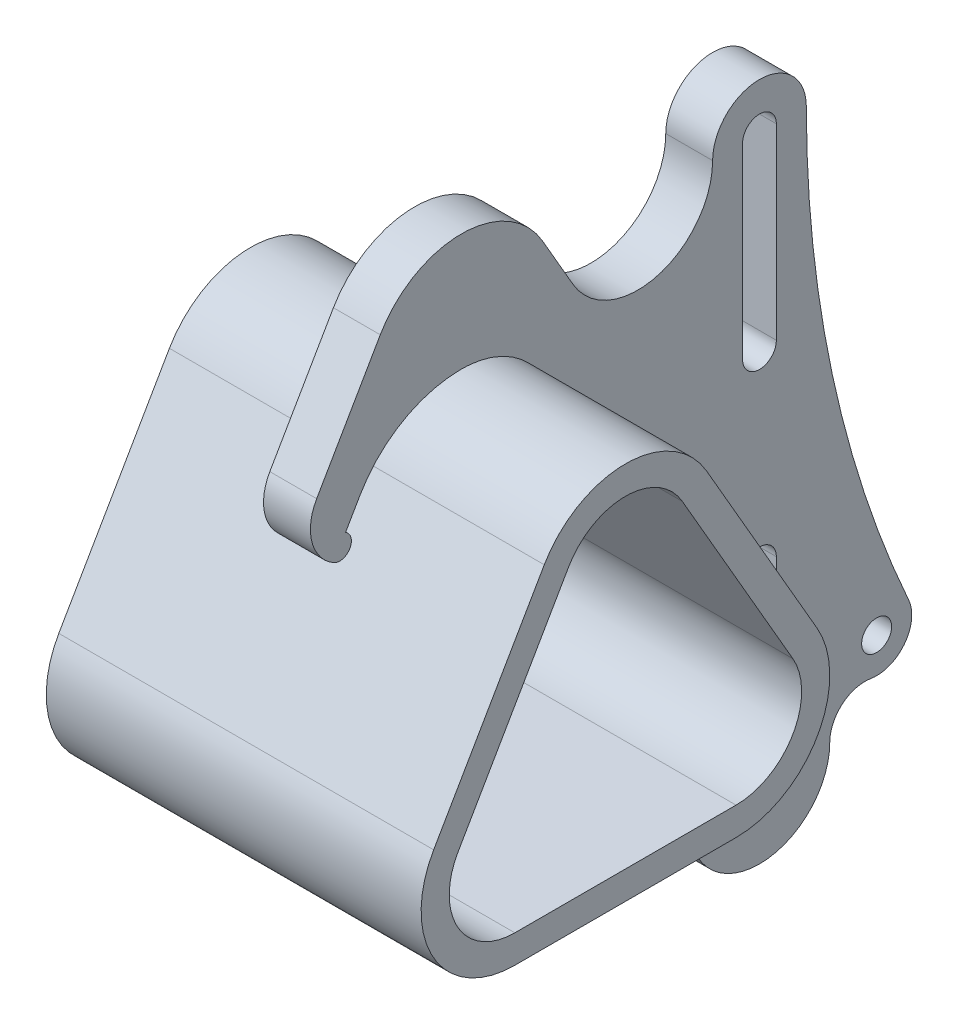
SolidWorks part; units mm, degrees
ref_plane "Front Plane" through (0, 0, 0) normal (0, 0, 1) x (1, 0, 0)
ref_plane "Top Plane" through (0, 0, 0) normal (0, 1, 0) x (1, 0, 0)
ref_plane "Right Plane" through (0, 0, 0) normal (1, 0, 0) x (0, 0, -1)
sketch "Sketch1" plane through (0, 0, 0) normal (1, 0, 0) x (0, 0, -1)
  line L0 (-9.525, 0) -> (-9.525, 27.9956)
  line L1 (-9.525, 27.9956) -> (-29.3888, 62.4007)
  line L2 (-14.4015, 36.4419) -> (-29.3888, 62.4007)
  line L3 (-51.3858, 62.4007) -> (-66.3732, 36.4419)
  line L4 (-55.3746, 17.3919) -> (-25.4, 17.3919)
  line L5 (-55.3746, 21.2019) -> (-25.4, 21.2019)
  line L6 (-48.0863, 60.4957) -> (-63.0736, 34.5369)
  line L7 (-17.701, 34.5369) -> (-32.6884, 60.4957)
  line L8 (-12.7, 30.0919) -> (-12.7, 3.0715) construction
  line L9 (-51.3858, 62.4007) -> (-47.8363, 68.5487) construction
  line L10 (-54.1355, 60.8132) -> (-56.0914, 57.4255)
  line L11 (-60.0031, 63.3501) -> (-51.3858, 78.2757)
  line L12 (-29.3888, 78.2757) -> (-25.2644, 71.1319)
  line L13 (-40.3873, 71.9257) -> (-23.8895, 71.9257) construction
  line L14 (-56.8851, 56.0507) -> (-40.3873, 56.0507) construction
  arc A0 (-9.525, 0) -> (9.525, 0) centre (0, 0) ccw
  arc A1 (-29.3888, 62.4007) -> (-40.3873, 68.7507) centre (-40.3873, 56.0507) ccw
  arc A2 (-14.4015, 36.4419) -> (-25.4, 17.3919) centre (-25.4, 30.0919) cw
  arc A3 (-29.3888, 62.4007) -> (-51.3858, 62.4007) centre (-40.3873, 56.0507) ccw
  arc A4 (-66.3732, 36.4419) -> (-55.3746, 17.3919) centre (-55.3746, 30.0919) ccw
  arc A5 (-17.701, 34.5369) -> (-25.4, 21.2019) centre (-25.4, 30.0919) cw
  arc A6 (-63.0736, 34.5369) -> (-55.3746, 21.2019) centre (-55.3746, 30.0919) ccw
  arc A7 (-32.6884, 60.4957) -> (-48.0863, 60.4957) centre (-40.3873, 56.0507) ccw
  arc A8 (-40.3873, 68.7507) -> (-51.3858, 62.4007) centre (-40.3873, 56.0507) ccw construction
  arc A9 (-40.3873, 68.7507) -> (-54.1355, 60.8132) centre (-40.3873, 52.8757) ccw
  arc A10 (-56.0914, 57.4255) -> (-57.6789, 54.6758) centre (-56.8851, 56.0507) cw
  arc A11 (-57.6789, 54.6758) -> (-60.0031, 63.3501) centre (-54.5039, 60.1751) cw
  arc A12 (-51.3858, 78.2757) -> (-29.3888, 78.2757) centre (-40.3873, 71.9257) cw
  arc A13 (-29.3888, 62.4007) -> (-51.3858, 62.4007) centre (-40.3873, 56.0507) ccw construction
  arc A14 (-25.2644, 71.1319) -> (-23.893, 73.5132) centre (-23.8895, 71.9257) ccw construction
  arc A16 (-6.35, 76.2) -> (6.35, 76.2) centre (0, 76.2) cw
  arc A17 (9.525, 0) -> (15.0813, 4.6959) centre (14.2875, 0) cw
  arc A18 (15.0813, 4.6959) -> (20.2209, 11.3397) centre (15.875, 9.3918) ccw
  arc A20 (6.35, 76.2) -> (20.2209, 11.3397) centre (164.9286, 76.2) ccw
  arc A21 (-66.3732, 36.4419) -> (-55.3746, 17.3919) centre (-55.3746, 30.0919) ccw construction
  arc A22 (-32.6884, 60.4957) -> (-48.0863, 60.4957) centre (-40.3873, 56.0507) ccw construction
  arc A23 (-25.2644, 71.1319) -> (-6.35, 76.2) centre (-16.4862, 76.2) ccw
  point P11 (-40.3873, 79.496)
  point P17 (-40.3873, 68.7507)
  point P18 (-40.3873, 17.3919)
  point P27 (-55.3746, 18.8051)
  point P45 (-40.3873, 97.3257)
  point P55 (0, 0)
  dimension "D1" = 12.7
  dimension "D6" = 60
  dimension "D7" = 1.5875
  dimension "D8" = 1.5875
  dimension "D9" = 12.7
  dimension "D12" = 6.35
  dimension "D13" = 9.525
  dimension "D15" = 4.7625
  dimension "D2" = 51.3588
  dimension "D4" = 3.175
  dimension "D5" = 150
  dimension "D10" = 6.35
  dimension "D11" = 12.7
  dimension "D14" = 15.875
  dimension "D16" = 76.2
  dimension "D3" = 3.81
extrude "Boss-Extrude1" add sketch "Sketch1" along normal mid plane 6.35 contours A23 L12 A12 L11 A11 A10 L10 A9 A1 L1 L0 A0 A17 A18 A20 A16 region at (0, 42.9084, 9.4146)
extrude "Boss-Extrude2" add sketch "Sketch1<3>" along normal mid plane 50.8 separate body contours L3 A4 L4 A2 L1 A1 A3 A7 L7 A5 L5 A6 L6 region at (0, 24.1195, 15.0555)
sketch "Sketch1<3>" plane through (0, 0, 0) normal (1, 0, 0) x (0, 0, -1) same geometry as "Sketch1"
sketch "Sketch2" plane through (3.175, 0, 0) normal (1, 0, 0) x (0, 0, -1)
  line L0 (0, 0) -> (0, 25.4) construction
  line L1 (-2.286, 0) -> (-2.286, 25.4)
  line L2 (2.286, 0) -> (2.286, 25.4)
  line L3 (0, 76.2) -> (0, 50.8) construction
  line L4 (2.286, 76.2) -> (2.286, 50.8)
  line L5 (-2.286, 76.2) -> (-2.286, 50.8)
  arc A0 (-2.286, 0) -> (2.286, 0) centre (0, 0) ccw
  arc A1 (2.286, 25.4) -> (-2.286, 25.4) centre (0, 25.4) ccw
  arc A2 (2.286, 76.2) -> (-2.286, 76.2) centre (0, 76.2) ccw
  arc A3 (-2.286, 50.8) -> (2.286, 50.8) centre (0, 50.8) ccw
  circle A4 centre (15.875, 9.3918) radius 2.032
  point P3 (0, 12.7)
  point P8 (0, 63.5)
  dimension "D2" = 4.572
  dimension "D3" = 4.064
  dimension "D1" = 25.4
extrude "Cut-Extrude1" cut sketch "Sketch2" against normal through all
